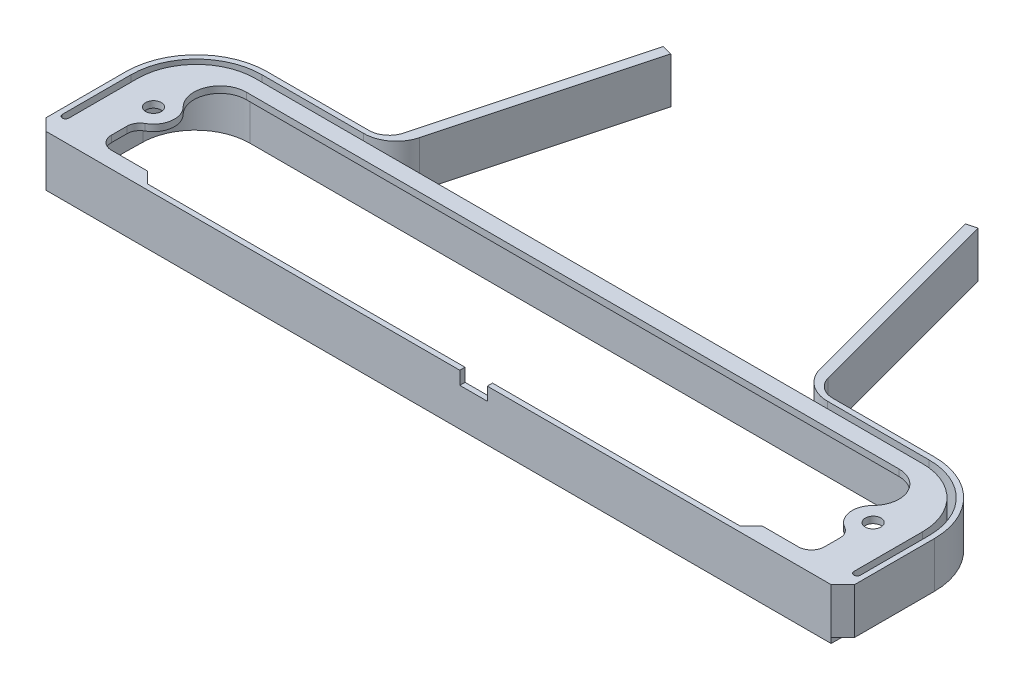
SolidWorks part; units mm, degrees
material "ABS"
ref_plane "Front" through (0, 0, 0) normal (0, 0, 1) x (1, 0, 0)
ref_plane "Top" through (0, 0, 0) normal (0, 1, 0) x (1, 0, 0)
ref_plane "Right" through (0, 0, 0) normal (1, 0, 0) x (0, 0, -1)
ref_axis "X" through (-80.9, 0, 0) along (1, 0, 0)
ref_axis "Y" through (0, -50, 0) along (0, 1, 0)
ref_axis "Z" through (0, 0, -80.9) along (0, 0, 1)
sketch "Sketch1" plane through (0, 0, 0) normal (0, 1, 0) x (1, 0, 0)
  line L0 (-60, 0) -> (-54.5, 0)
  line L2 (-49.8878, 20.5) -> (49.8878, 20.5)
  line L4 (54.5, 0) -> (60, 0)
  line L5 (60, 0) -> (60, 14)
  line L6 (51, 23) -> (-51, 23)
  line L7 (-60, 14) -> (-60, 0)
  line L8 (-54.5, 0) -> (54.5, 0)
  line L9 (-47, 0.8) -> (47, 0.8)
  line L10 (-54.5, 0) -> (-54.5, 0.8) construction
  line L11 (54.5, 0) -> (54.5, 0.8) construction
  line L12 (55, 11.43) -> (-55, 11.43) construction
  line L13 (0, 11.43) -> (0, 0) construction
  line L14 (54.5, 2.5) -> (47, 2.5)
  line L15 (47, 2.5) -> (47, 0.8)
  line L16 (-54.5, 2.5) -> (-47, 2.5)
  line L17 (-47, 2.5) -> (-47, 0.8)
  line L18 (-54.5, 0.8) -> (-54.5, 2.5) construction
  line L19 (-54.5, 0.8) -> (-47, 0.8) construction
  line L20 (54.5, 2.5) -> (54.5, 0.8) construction
  line L21 (47, 0.8) -> (54.5, 0.8) construction
  line L22 (54.5, 8.2693) -> (54.5, 2.5)
  line L23 (-54.5, 2.5) -> (-54.5, 8.2693)
  arc A0 (-52.7279, 13.6833) -> (-49.8878, 20.5) centre (-49.8878, 16.5) cw
  arc A1 (49.8878, 20.5) -> (52.7279, 13.6833) centre (49.8878, 16.5) cw
  arc A2 (60, 14) -> (51, 23) centre (51, 14) ccw
  arc A3 (-51, 23) -> (-60, 14) centre (-51, 14) ccw
  circle A4 centre (55, 11.43) radius 1.2
  circle A5 centre (-55, 11.43) radius 1.2
  arc A6 (52.7279, 13.6833) -> (54.5, 8.2693) centre (55, 11.43) ccw
  arc A7 (-52.7279, 13.6833) -> (-54.5, 8.2693) centre (-55, 11.43) cw
  dimension "D5" = 9
  dimension "D6" = 4
  dimension "D10" = 2.4
  dimension "D13" = 3.2
  dimension "D1" = 120
  dimension "D2" = 5.5
  dimension "D3" = 2.5
  dimension "D4" = 23
  dimension "D7" = 0.8
  dimension "D8" = 11.43
  dimension "D9" = 110
  dimension "D11" = 13
  dimension "D12" = 2.5
extrude "Boss-Extrude1" add sketch "Sketch1" along normal blind 1
sketch "Sketch8" plane through (0, 0, 0) normal (0, -1, 0) x (-1, 0, 0)
  line L0 (-59.2, 0.8) -> (59.2, 0.8)
  line L1 (59.2, 0.8) -> (59.2, 14)
  line L2 (51, 22.2) -> (-51, 22.2)
  line L3 (-59.2, 14) -> (-59.2, 0.8)
  line L4 (60, 0) -> (60, 14)
  line L5 (51, 23) -> (-51, 23)
  line L6 (-60, 14) -> (-60, 0)
  line L7 (-60, 0) -> (60, 0)
  line L8 (60, 0) -> (60, 14)
  line L9 (51, 23) -> (-51, 23)
  line L10 (-60, 14) -> (-60, 0)
  line L11 (-60, 0) -> (60, 0)
  arc A0 (59.2, 14) -> (51, 22.2) centre (51, 14) ccw
  arc A1 (-51, 22.2) -> (-59.2, 14) centre (-51, 14) ccw
  arc A2 (60, 14) -> (51, 23) centre (51, 14) ccw
  arc A3 (-51, 23) -> (-60, 14) centre (-51, 14) ccw
  arc A4 (60, 14) -> (51, 23) centre (51, 14) ccw
  arc A5 (-51, 23) -> (-60, 14) centre (-51, 14) ccw
  dimension "D1" = 0
  dimension "D2" = 0.8
extrude "Boss-Extrude2" add sketch "Sketch8" along normal blind 8.2 from surface starting at face at (55, 1, -10.23)
chamfer "Chamfer1" distance 1 angle 45 7 edges at (59.2, 0, -7.4) (56.7983, 0, -19.7983) (-59.2, 0, -7.4) (-56.7983, 0, -19.7983) (53.1, 0, -0.8) (-53.1, 0, -0.8) (0, 0, -22.2)
sketch "Sketch9" plane through (0, 0, 0) normal (1, 0, 0) x (0, 0, -1)
  line L0 (-2, -7.2) -> (23, -7.2)
  line L1 (23, -7.2) -> (-2, -6.7636)
  line L3 (-2, -6.7636) -> (-2, -7.2)
  dimension "D1" = 25
  dimension "D2" = 1
extrude "Cut-Extrude1" cut sketch "Sketch9" against normal through all both and the other way through all
sketch "Sketch11" plane through (0, 0, 0) normal (0, 0, 1) x (1, 0, 0)
  line L0 (3.25, 1) -> (3.25, -1)
  line L1 (-60, 1) -> (60, 1) construction
  line L2 (3.25, -1) -> (7.45, -1)
  line L3 (7.45, -1) -> (7.45, 1)
  line L4 (7.45, 1) -> (3.25, 1)
  line L5 (5.35, -1) -> (5.35, 1) construction
  line L7 (60, 1) -> (60, -6.7985) construction
  dimension "D1" = 54.65
  dimension "D2" = 4.2
  dimension "D3" = 2
extrude "Cut-Extrude2" cut sketch "Sketch11" against normal up to next
fillet "Fillet1" radius 2 4 edges at (-54.5, 0.5, -8.2693) (-54.5, 0.5, -2.5) (54.5, 0.5, -2.5) (54.5, 0.5, -8.2693)
chamfer "Chamfer2" distance 1.7 angle 45 2 edges at (-47, 0, -0.8) (47, 0, -0.8)
sketch "Sketch12" plane through (0, 0, 0) normal (0, 1, 0) x (1, 0, 0)
  line L0 (-35.4469, 24) -> (-35.4469, 24.8) construction
  line L1 (-60, 0) -> (60, 0) construction
  line L3 (-70.0161, 72.0463) -> (123.9526, 72.0463) construction
  line L9 (-60, 0) -> (-61.8, 1.8)
  line L10 (7.45, 0) -> (60, 0) construction
  line L11 (0, 38.0905) -> (0, 0) construction
  line L21 (-30.6173, 27.7059) -> (-22.5, 58)
  line L22 (-22.5, 58) -> (-24.0455, 58.4141)
  line L23 (-24.0455, 58.4141) -> (-32.4326, 27.113)
  line L27 (51, 23) -> (-51, 23) construction
  line L31 (-60, 0) -> (-60, 3.5)
  line L32 (-60, 14) -> (-60, 0) construction
  line L34 (-61.8, 1.8) -> (-61.8, 14)
  line L35 (-51, 24.8) -> (-35.4469, 24.8)
  line L36 (-61, 3.5) -> (-61, 14)
  line L37 (-51, 24) -> (-35.4469, 24)
  line L39 (-51, 24) -> (-51, 24.8) construction
  line L40 (-61, 14) -> (-61.8, 14) construction
  arc A3 (-61.8, 14) -> (-51, 24.8) centre (-51, 14) cw
  arc A4 (-61, 14) -> (-51, 24) centre (-51, 14) cw
  arc A5 (-61, 3.5) -> (-60, 3.5) centre (-60.5, 3.5) ccw
  arc A7 (-51, 23) -> (-60, 14) centre (-51, 14) ccw construction
  arc A8 (-35.4469, 24) -> (-30.6173, 27.7059) centre (-35.4469, 29) ccw
  arc A9 (-35.4469, 24.8) -> (-32.4326, 27.113) centre (-35.4469, 27.9206) ccw
  dimension "D7" = 5
  dimension "D3" = 72.0463
  dimension "D9" = 15
  dimension "D11" = 35
  dimension "D12" = 1.6
  dimension "D14" = 22.5
  dimension "D2" = 45
  dimension "D4" = 1
  dimension "D5" = 0.8
  dimension "D6" = 3.5
extrude "Boss-Extrude3" add sketch "Sketch12" against normal blind 7 from surface starting at face at (0.8231, 1, -7.7026)
mirror "Mirror2" about plane through (0, 0, 0) normal (1, 0, 0) of "Boss-Extrude3"
equation "\"D3@Sketch12\"=200-127.95373"
